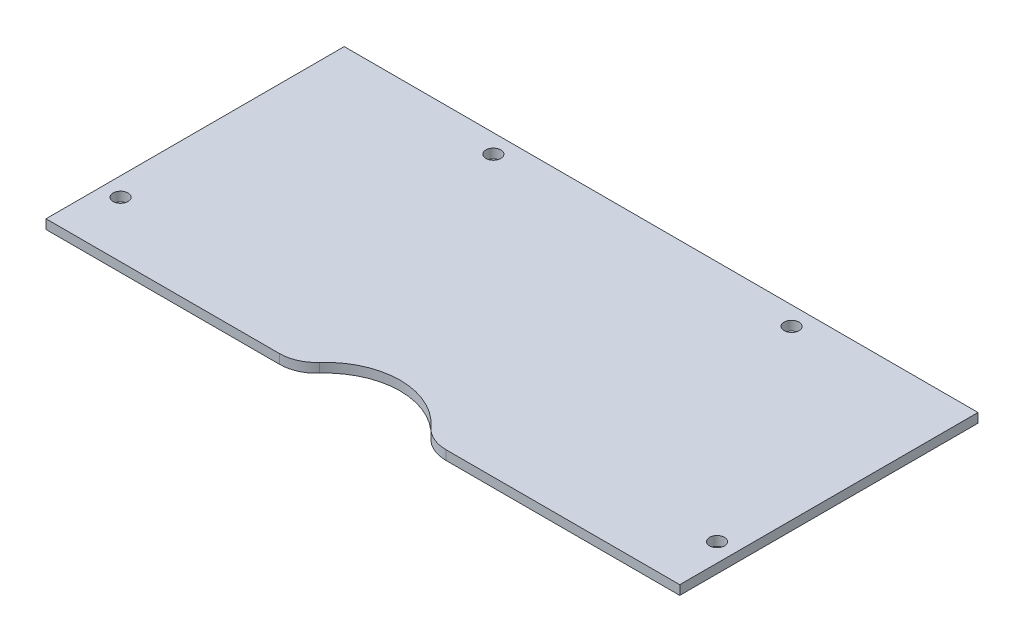
SolidWorks part; units mm, degrees
material "Zoltek Panex 33"
ref_plane "Front Plane" through (0, 0, 0) normal (0, 0, 1) x (1, 0, 0)
ref_plane "Top Plane" through (0, 0, 0) normal (0, 1, 0) x (1, 0, 0)
ref_plane "Right Plane" through (0, 0, 0) normal (1, 0, 0) x (0, 0, -1)
sketch "Sketch1" plane through (0, 0, 0) normal (0, 1, 0) x (1, 0, 0)
  line L0 (0, 101.6) -> (0, 0)
  line L1 (0, 0) -> (215.9, 0)
  line L2 (0, 0) -> (0, 228.6)
  line L3 (0, 228.6) -> (215.9, 228.6)
  line L4 (215.9, 0) -> (215.9, 228.6)
  line L5 (0, 127) -> (85.953, 127)
  line L6 (0, 127) -> (0, 101.6)
  line L7 (0, 101.6) -> (85.953, 101.6)
  line L8 (85.953, 127) -> (85.953, 101.6)
  line L9 (215.9, 127) -> (129.947, 127)
  line L10 (215.9, 127) -> (215.9, 101.6)
  line L11 (215.9, 101.6) -> (129.947, 101.6)
  line L12 (129.947, 127) -> (129.947, 101.6)
  line L13 (215.9, 0) -> (215.9, 101.6)
  circle A0 centre (107.95, 114.3) radius 25.4
  point P13 (85.953, 114.3)
  point P18 (0, 114.3)
  dimension "D4" = 50.8
  dimension "D5" = 85.953
  dimension "D1" = 228.6
  dimension "D2" = 215.9
  dimension "D3" = 25.4
extrude "Boss-Extrude1" add sketch "Sketch1" along normal blind 3.175 contours A0 L9 L4 L3 L2 L5 region at (107.95, 0, -178.6387)
fillet "Fillet1" radius 12.7 2 edges at (129.947, 1.5875, -127) (85.953, 1.5875, -127)
sketch "Sketch2" plane through (0, 3.175, 0) normal (0, 1, 0) x (1, 0, 0)
  line L0 (0, 127) -> (0, 228.6) construction
  line L1 (0, 228.6) -> (215.9, 228.6) construction
  line L2 (215.9, 127) -> (215.9, 228.6) construction
  line L3 (0, 127) -> (79.5519, 127) construction
  line L4 (215.9, 127) -> (136.3481, 127) construction
  circle A0 centre (6.35, 146.05) radius 2.54
  circle A1 centre (57.15, 222.25) radius 2.54
  circle A2 centre (158.75, 222.25) radius 2.54
  circle A3 centre (209.55, 146.05) radius 2.54
  dimension "D1" = 5.08
  dimension "D2" = 6.35
  dimension "D3" = 6.35
  dimension "D4" = 6.35
  dimension "D5" = 6.35
  dimension "D6" = 57.15
  dimension "D7" = 19.05
  dimension "D8" = 57.15
  dimension "D9" = 19.05
extrude "Cut-Extrude1" cut sketch "Sketch2" against normal through all
